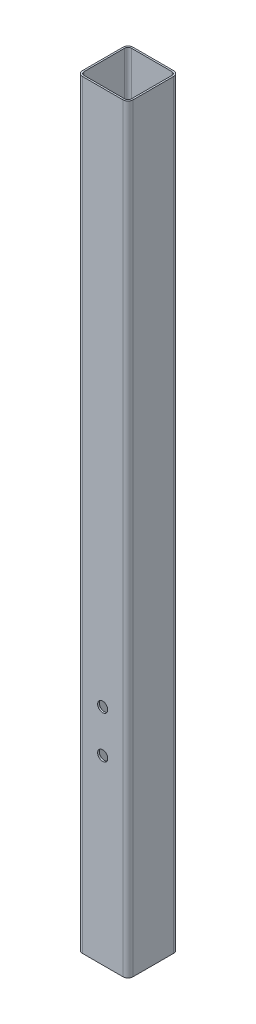
SolidWorks part; units mm, degrees
material "Plain Carbon Steel"
ref_plane "Front Plane" through (0, 0, 0) normal (0, 0, 1) x (1, 0, 0)
ref_plane "Top Plane" through (0, 0, 0) normal (0, 1, 0) x (1, 0, 0)
ref_plane "Right Plane" through (0, 0, 0) normal (1, 0, 0) x (0, 0, -1)
sketch "Sketch1" plane through (0, 0, 0) normal (0, 1, 0) x (1, 0, 0)
  line L1 (-24, -30) -> (24, -30)
  line L2 (-30, -24) -> (-30, 24)
  line L3 (-24, 30) -> (24, 30)
  line L4 (30, -24) -> (30, 24)
  line L5 (-30, -30) -> (30, 30) construction
  line L6 (-30, 30) -> (30, -30) construction
  arc A0 (30, -24) -> (24, -30) centre (24, -24) cw
  arc A1 (30, 24) -> (24, 30) centre (24, 24) ccw
  arc A2 (-24, 30) -> (-30, 24) centre (-24, 24) ccw
  arc A3 (-24, -30) -> (-30, -24) centre (-24, -24) cw
  point P0 (0, 0)
  dimension "D3" = 6
  dimension "D1" = 60
  dimension "D2" = 60
extrude "Boss-Extrude1" add sketch "Sketch1" along normal mid plane 900
shell "Shell1" thickness 2 removed face at (0, -450, 0) removed face at (0, 450, 0)
sketch "Sketch2" [suppressed] plane through (0, 0, -30) normal (0, 0, -1) x (-1, 0, 0)
  line L1 (-15.5, 18.5021) -> (15.5, 18.5021)
  line L2 (-15.5, 18.5021) -> (-15.5, -12.4979)
  line L3 (-15.5, -12.4979) -> (15.5, -12.4979)
  line L4 (15.5, 18.5021) -> (15.5, -12.4979)
  line L5 (-15.5, 18.5021) -> (15.5, -12.4979) construction
  line L6 (-15.5, -12.4979) -> (15.5, 18.5021) construction
  line L7 (0, 33) -> (0, -33) construction
  line L9 (-27.4108, 3.0021) -> (27.4108, 3.0021) construction
  point P0 (0, 3.0021)
  dimension "D1" = 31
  dimension "D2" = 31
extrude "Cut-Extrude1" [suppressed] cut sketch "Sketch2" against normal through all
sketch "Sketch3" [suppressed] plane through (0, 0, -30) normal (0, 0, -1) x (-1, 0, 0)
  circle A0 centre (0, 0) radius 17.5
  dimension "D1" = 35
extrude "Cut-Extrude2" [suppressed] cut sketch "Sketch3" against normal through all
sketch "Sketch4" plane through (0, 0, -30) normal (0, 0, -1) x (-1, 0, 0)
  circle A0 centre (0, -235) radius 6 construction
  circle A1 centre (0, -185) radius 6 construction
  circle A2 centre (0, -235) radius 6
  circle A3 centre (0, -185) radius 6
extrude "Cut-Extrude3" cut sketch "Sketch4" against normal through all
